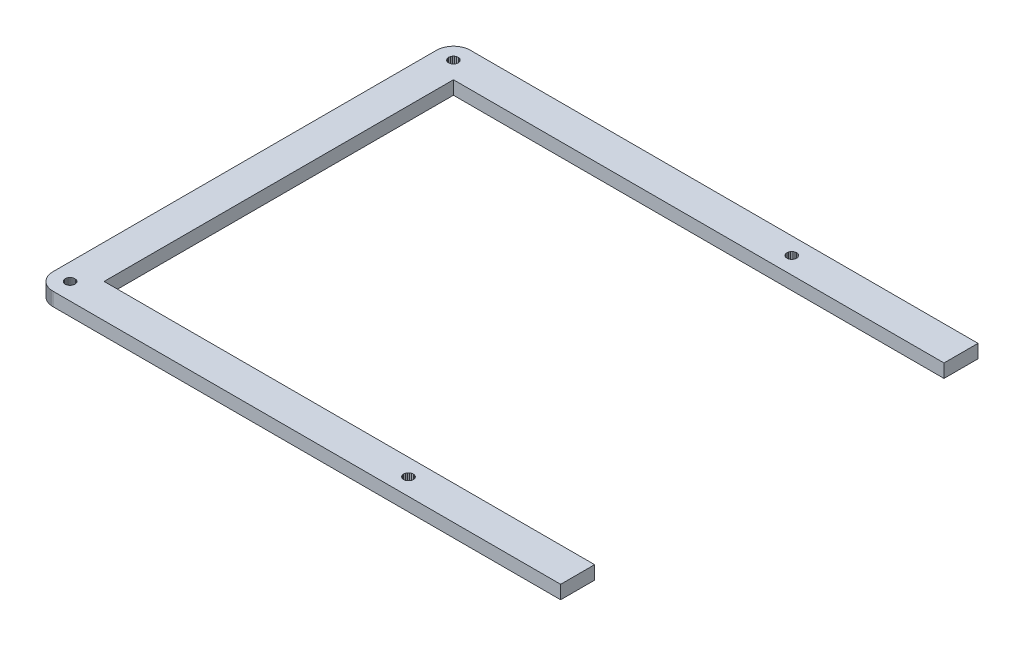
SolidWorks part; units mm, degrees
material "Copper"
ref_plane "Front Plane" through (0, 0, 0) normal (0, 0, 1) x (1, 0, 0)
ref_plane "Top Plane" through (0, 0, 0) normal (0, 1, 0) x (1, 0, 0)
ref_plane "Right Plane" through (0, 0, 0) normal (1, 0, 0) x (0, 0, -1)
sketch "Sketch1" plane through (0, 0, 0) normal (0, 1, 0) x (1, 0, 0)
  line L0 (365.806, 147.967) -> (366.279, 147.949)
  line L1 (366.279, 147.949) -> (366.748, 147.894)
  line L2 (366.748, 147.894) -> (367.21, 147.803)
  line L3 (367.21, 147.803) -> (367.661, 147.675)
  line L4 (367.661, 147.675) -> (368.106, 147.511)
  line L5 (368.106, 147.511) -> (368.533, 147.314)
  line L6 (368.533, 147.314) -> (368.942, 147.085)
  line L7 (368.942, 147.085) -> (369.334, 146.822)
  line L8 (369.334, 146.822) -> (369.704, 146.529)
  line L9 (369.704, 146.529) -> (370.05, 146.21)
  line L10 (370.05, 146.21) -> (370.371, 145.865)
  line L11 (370.371, 145.865) -> (370.664, 145.495)
  line L12 (370.664, 145.495) -> (370.925, 145.102)
  line L13 (370.925, 145.102) -> (371.154, 144.691)
  line L14 (371.154, 144.691) -> (371.352, 144.264)
  line L15 (371.352, 144.264) -> (371.514, 143.822)
  line L16 (371.514, 143.822) -> (371.641, 143.368)
  line L17 (371.641, 143.368) -> (371.733, 142.907)
  line L18 (371.733, 142.907) -> (371.789, 142.44)
  line L19 (371.789, 142.44) -> (371.807, 141.967)
  line L20 (371.807, 141.967) -> (371.807, 6.0909)
  line L21 (371.807, 6.0909) -> (371.789, 5.621)
  line L22 (371.789, 5.621) -> (371.733, 5.1539)
  line L23 (371.733, 5.1539) -> (371.641, 4.6909)
  line L24 (371.641, 4.6909) -> (371.514, 4.2375)
  line L25 (371.514, 4.2375) -> (371.352, 3.7951)
  line L26 (371.352, 3.7951) -> (371.154, 3.3679)
  line L27 (371.154, 3.3679) -> (370.925, 2.9573)
  line L28 (370.925, 2.9573) -> (370.664, 2.5645)
  line L29 (370.664, 2.5645) -> (370.371, 2.1966)
  line L30 (370.371, 2.1966) -> (370.05, 1.8493)
  line L31 (370.05, 1.8493) -> (369.704, 1.5296)
  line L32 (369.704, 1.5296) -> (369.334, 1.2375)
  line L33 (369.334, 1.2375) -> (368.942, 0.9757)
  line L34 (368.942, 0.9757) -> (368.533, 0.7455)
  line L35 (368.533, 0.7455) -> (368.106, 0.5498)
  line L36 (368.106, 0.5498) -> (367.661, 0.3859)
  line L37 (367.661, 0.3859) -> (367.21, 0.2577)
  line L38 (367.21, 0.2577) -> (366.748, 0.1654)
  line L39 (366.748, 0.1654) -> (366.279, 0.1102)
  line L40 (366.279, 0.1102) -> (365.806, 0.091)
  line L41 (365.806, 0.091) -> (6.095, 0.091)
  line L42 (6.095, 0.091) -> (5.6238, 0.1102)
  line L43 (5.6238, 0.1102) -> (5.1553, 0.1654)
  line L44 (5.1553, 0.1654) -> (4.6936, 0.2577)
  line L45 (4.6936, 0.2577) -> (4.2402, 0.3859)
  line L46 (4.2402, 0.3859) -> (3.7979, 0.5498)
  line L47 (3.7979, 0.5498) -> (3.3707, 0.7455)
  line L48 (3.3707, 0.7455) -> (2.96, 0.9757)
  line L49 (2.96, 0.9757) -> (2.5673, 1.2375)
  line L50 (2.5673, 1.2375) -> (2.198, 1.5296)
  line L51 (2.198, 1.5296) -> (1.8521, 1.8493)
  line L52 (1.8521, 1.8493) -> (1.5324, 2.1966)
  line L53 (1.5324, 2.1966) -> (1.2402, 2.5645)
  line L54 (1.2402, 2.5645) -> (0.9784, 2.9573)
  line L55 (0.9784, 2.9573) -> (0.7483, 3.3679)
  line L56 (0.7483, 3.3679) -> (0.5512, 3.7951)
  line L57 (0.5512, 3.7951) -> (0.3872, 4.2375)
  line L58 (0.3872, 4.2375) -> (0.2591, 4.6909)
  line L59 (0.2591, 4.6909) -> (0.1681, 5.1539)
  line L60 (0.1681, 5.1539) -> (0.113, 5.621)
  line L61 (0.113, 5.621) -> (0.0937, 6.0923)
  line L62 (0.0937, 6.0923) -> (0.0951, 141.967)
  line L63 (0.0951, 141.967) -> (0.113, 142.44)
  line L64 (0.113, 142.44) -> (0.1681, 142.907)
  line L65 (0.1681, 142.907) -> (0.2591, 143.368)
  line L66 (0.2591, 143.368) -> (0.3872, 143.822)
  line L67 (0.3872, 143.822) -> (0.5512, 144.264)
  line L68 (0.5512, 144.264) -> (0.7483, 144.691)
  line L69 (0.7483, 144.691) -> (0.9784, 145.102)
  line L70 (0.9784, 145.102) -> (1.2402, 145.495)
  line L71 (1.2402, 145.495) -> (1.5324, 145.865)
  line L72 (1.5324, 145.865) -> (1.8521, 146.21)
  line L73 (1.8521, 146.21) -> (2.198, 146.529)
  line L74 (2.198, 146.529) -> (2.5673, 146.822)
  line L75 (2.5673, 146.822) -> (2.96, 147.085)
  line L76 (2.96, 147.085) -> (3.3707, 147.314)
  line L77 (3.3707, 147.314) -> (3.7979, 147.511)
  line L78 (3.7979, 147.511) -> (4.2402, 147.675)
  line L79 (4.2402, 147.675) -> (4.6936, 147.803)
  line L80 (4.6936, 147.803) -> (5.1553, 147.894)
  line L81 (5.1553, 147.894) -> (5.6238, 147.949)
  line L82 (5.6238, 147.949) -> (6.095, 147.968)
  line L83 (6.095, 147.968) -> (365.806, 147.967)
  line L84 (365.252, 7.757) -> (364.769, 7.5117)
  line L85 (364.769, 7.5117) -> (364.388, 7.13)
  line L86 (364.388, 7.13) -> (364.141, 6.6504)
  line L87 (364.141, 6.6504) -> (364.06, 6.1157)
  line L88 (364.06, 6.1157) -> (364.141, 5.5838)
  line L89 (364.141, 5.5838) -> (364.388, 5.1029)
  line L90 (364.388, 5.1029) -> (364.769, 4.7211)
  line L91 (364.769, 4.7211) -> (365.252, 4.4759)
  line L92 (365.252, 4.4759) -> (365.781, 4.3918)
  line L93 (365.781, 4.3918) -> (366.317, 4.4759)
  line L94 (366.317, 4.4759) -> (366.797, 4.7211)
  line L95 (366.797, 4.7211) -> (367.178, 5.1029)
  line L96 (367.178, 5.1029) -> (367.425, 5.5838)
  line L97 (367.425, 5.5838) -> (367.506, 6.1157)
  line L98 (367.506, 6.1157) -> (367.425, 6.6504)
  line L99 (367.425, 6.6504) -> (367.178, 7.13)
  line L100 (367.178, 7.13) -> (366.797, 7.5117)
  line L101 (366.797, 7.5117) -> (366.317, 7.757)
  line L102 (366.317, 7.757) -> (365.781, 7.8411)
  line L103 (365.781, 7.8411) -> (365.252, 7.757)
  line L104 (245.361, 7.757) -> (244.88, 7.5117)
  line L105 (244.88, 7.5117) -> (244.5, 7.13)
  line L106 (244.5, 7.13) -> (244.255, 6.6504)
  line L107 (244.255, 6.6504) -> (244.169, 6.1157)
  line L108 (244.169, 6.1157) -> (244.255, 5.5838)
  line L109 (244.255, 5.5838) -> (244.5, 5.1029)
  line L110 (244.5, 5.1029) -> (244.88, 4.7211)
  line L111 (244.88, 4.7211) -> (245.361, 4.4759)
  line L112 (245.361, 4.4759) -> (245.894, 4.3918)
  line L113 (245.894, 4.3918) -> (246.428, 4.4759)
  line L114 (246.428, 4.4759) -> (246.908, 4.7211)
  line L115 (246.908, 4.7211) -> (247.29, 5.1029)
  line L116 (247.29, 5.1029) -> (247.536, 5.5838)
  line L117 (247.536, 5.5838) -> (247.62, 6.1157)
  line L118 (247.62, 6.1157) -> (247.536, 6.6504)
  line L119 (247.536, 6.6504) -> (247.29, 7.13)
  line L120 (247.29, 7.13) -> (246.908, 7.5117)
  line L121 (246.908, 7.5117) -> (246.428, 7.757)
  line L122 (246.428, 7.757) -> (245.894, 7.8411)
  line L123 (245.894, 7.8411) -> (245.361, 7.757)
  line L124 (125.473, 7.757) -> (124.992, 7.5117)
  line L125 (124.992, 7.5117) -> (124.612, 7.13)
  line L126 (124.612, 7.13) -> (124.365, 6.6504)
  line L127 (124.365, 6.6504) -> (124.281, 6.1157)
  line L128 (124.281, 6.1157) -> (124.365, 5.5838)
  line L129 (124.365, 5.5838) -> (124.612, 5.1029)
  line L130 (124.612, 5.1029) -> (124.992, 4.7211)
  line L131 (124.992, 4.7211) -> (125.473, 4.4759)
  line L132 (125.473, 4.4759) -> (126.007, 4.3918)
  line L133 (126.007, 4.3918) -> (126.54, 4.4759)
  line L134 (126.54, 4.4759) -> (127.021, 4.7211)
  line L135 (127.021, 4.7211) -> (127.403, 5.1029)
  line L136 (127.403, 5.1029) -> (127.648, 5.5838)
  line L137 (127.648, 5.5838) -> (127.732, 6.1157)
  line L138 (127.732, 6.1157) -> (127.648, 6.6504)
  line L139 (127.648, 6.6504) -> (127.403, 7.13)
  line L140 (127.403, 7.13) -> (127.021, 7.5117)
  line L141 (127.021, 7.5117) -> (126.54, 7.757)
  line L142 (126.54, 7.757) -> (126.007, 7.8411)
  line L143 (126.007, 7.8411) -> (125.473, 7.757)
  line L144 (5.5852, 7.757) -> (5.1056, 7.5117)
  line L145 (5.1056, 7.5117) -> (4.7239, 7.13)
  line L146 (4.7239, 7.13) -> (4.4786, 6.6504)
  line L147 (4.4786, 6.6504) -> (4.3932, 6.1157)
  line L148 (4.3932, 6.1157) -> (4.4786, 5.5838)
  line L149 (4.4786, 5.5838) -> (4.7239, 5.1029)
  line L150 (4.7239, 5.1029) -> (5.1056, 4.7211)
  line L151 (5.1056, 4.7211) -> (5.5852, 4.4759)
  line L152 (5.5852, 4.4759) -> (6.1185, 4.3918)
  line L153 (6.1185, 4.3918) -> (6.6532, 4.4759)
  line L154 (6.6532, 4.4759) -> (7.1327, 4.7211)
  line L155 (7.1327, 4.7211) -> (7.5145, 5.1029)
  line L156 (7.5145, 5.1029) -> (7.7597, 5.5838)
  line L157 (7.7597, 5.5838) -> (7.8438, 6.1157)
  line L158 (7.8438, 6.1157) -> (7.7597, 6.6504)
  line L159 (7.7597, 6.6504) -> (7.5145, 7.13)
  line L160 (7.5145, 7.13) -> (7.1327, 7.5117)
  line L161 (7.1327, 7.5117) -> (6.6532, 7.757)
  line L162 (6.6532, 7.757) -> (6.1185, 7.8411)
  line L163 (6.1185, 7.8411) -> (5.5852, 7.757)
  line L164 (12.1447, 135.919) -> (359.759, 135.919)
  line L165 (359.759, 135.919) -> (359.759, 12.1405)
  line L166 (359.759, 12.1405) -> (12.1447, 12.1405)
  line L167 (12.1447, 12.1405) -> (12.1447, 135.919)
  line L168 (125.473, 143.583) -> (124.992, 143.338)
  line L169 (124.992, 143.338) -> (124.612, 142.956)
  line L170 (124.612, 142.956) -> (124.365, 142.477)
  line L171 (124.365, 142.477) -> (124.281, 141.942)
  line L172 (124.281, 141.942) -> (124.365, 141.409)
  line L173 (124.365, 141.409) -> (124.612, 140.929)
  line L174 (124.612, 140.929) -> (124.992, 140.547)
  line L175 (124.992, 140.547) -> (125.473, 140.302)
  line L176 (125.473, 140.302) -> (126.007, 140.217)
  line L177 (126.007, 140.217) -> (126.54, 140.302)
  line L178 (126.54, 140.302) -> (127.021, 140.547)
  line L179 (127.021, 140.547) -> (127.403, 140.929)
  line L180 (127.403, 140.929) -> (127.648, 141.409)
  line L181 (127.648, 141.409) -> (127.732, 141.942)
  line L182 (127.732, 141.942) -> (127.648, 142.477)
  line L183 (127.648, 142.477) -> (127.403, 142.956)
  line L184 (127.403, 142.956) -> (127.021, 143.338)
  line L185 (127.021, 143.338) -> (126.54, 143.583)
  line L186 (126.54, 143.583) -> (126.007, 143.667)
  line L187 (126.007, 143.667) -> (125.473, 143.583)
  line L188 (245.361, 143.583) -> (244.88, 143.338)
  line L189 (244.88, 143.338) -> (244.5, 142.956)
  line L190 (244.5, 142.956) -> (244.255, 142.477)
  line L191 (244.255, 142.477) -> (244.169, 141.942)
  line L192 (244.169, 141.942) -> (244.255, 141.409)
  line L193 (244.255, 141.409) -> (244.5, 140.929)
  line L194 (244.5, 140.929) -> (244.88, 140.547)
  line L195 (244.88, 140.547) -> (245.361, 140.302)
  line L196 (245.361, 140.302) -> (245.894, 140.217)
  line L197 (245.894, 140.217) -> (246.428, 140.302)
  line L198 (246.428, 140.302) -> (246.908, 140.547)
  line L199 (246.908, 140.547) -> (247.29, 140.929)
  line L200 (247.29, 140.929) -> (247.536, 141.409)
  line L201 (247.536, 141.409) -> (247.62, 141.942)
  line L202 (247.62, 141.942) -> (247.536, 142.477)
  line L203 (247.536, 142.477) -> (247.29, 142.956)
  line L204 (247.29, 142.956) -> (246.908, 143.338)
  line L205 (246.908, 143.338) -> (246.428, 143.583)
  line L206 (246.428, 143.583) -> (245.894, 143.667)
  line L207 (245.894, 143.667) -> (245.361, 143.583)
  line L208 (365.252, 143.583) -> (364.769, 143.338)
  line L209 (364.769, 143.338) -> (364.388, 142.956)
  line L210 (364.388, 142.956) -> (364.141, 142.477)
  line L211 (364.141, 142.477) -> (364.06, 141.942)
  line L212 (364.06, 141.942) -> (364.141, 141.409)
  line L213 (364.141, 141.409) -> (364.388, 140.929)
  line L214 (364.388, 140.929) -> (364.769, 140.547)
  line L215 (364.769, 140.547) -> (365.252, 140.302)
  line L216 (365.252, 140.302) -> (365.781, 140.217)
  line L217 (365.781, 140.217) -> (366.317, 140.302)
  line L218 (366.317, 140.302) -> (366.797, 140.547)
  line L219 (366.797, 140.547) -> (367.178, 140.929)
  line L220 (367.178, 140.929) -> (367.425, 141.409)
  line L221 (367.425, 141.409) -> (367.506, 141.942)
  line L222 (367.506, 141.942) -> (367.425, 142.477)
  line L223 (367.425, 142.477) -> (367.178, 142.956)
  line L224 (367.178, 142.956) -> (366.797, 143.338)
  line L225 (366.797, 143.338) -> (366.317, 143.583)
  line L226 (366.317, 143.583) -> (365.781, 143.667)
  line L227 (365.781, 143.667) -> (365.252, 143.583)
  line L228 (5.5852, 143.583) -> (5.1056, 143.338)
  line L229 (5.1056, 143.338) -> (4.7239, 142.956)
  line L230 (4.7239, 142.956) -> (4.4786, 142.477)
  line L231 (4.4786, 142.477) -> (4.3932, 141.942)
  line L232 (4.3932, 141.942) -> (4.4786, 141.409)
  line L233 (4.4786, 141.409) -> (4.7239, 140.929)
  line L234 (4.7239, 140.929) -> (5.1056, 140.547)
  line L235 (5.1056, 140.547) -> (5.5852, 140.302)
  line L236 (5.5852, 140.302) -> (6.1185, 140.217)
  line L237 (6.1185, 140.217) -> (6.6532, 140.302)
  line L238 (6.6532, 140.302) -> (7.1327, 140.547)
  line L239 (7.1327, 140.547) -> (7.5145, 140.929)
  line L240 (7.5145, 140.929) -> (7.7597, 141.409)
  line L241 (7.7597, 141.409) -> (7.8438, 141.942)
  line L242 (7.8438, 141.942) -> (7.7597, 142.477)
  line L243 (7.7597, 142.477) -> (7.5145, 142.956)
  line L244 (7.5145, 142.956) -> (7.1327, 143.338)
  line L245 (7.1327, 143.338) -> (6.6532, 143.583)
  line L246 (6.6532, 143.583) -> (6.1185, 143.667)
  line L247 (6.1185, 143.667) -> (5.5852, 143.583)
  line L248 (185.9505, 147.9675) -> (185.9505, 0.091)
extrude "Boss-Extrude2" add sketch "Sketch1" along normal blind 4.7625 contours L248 L83 L82 L81 L80 L79 L78 L77 L76 L75 L74 L73 L72 L71 L70 L69 L68 L67 L66 L65 L64 L63 L62 L61 L60 L59 L58 L57 L56 L55 L54 L53 L52 L51 L50 L49 L48 L47 L46 L45 L44 L43 L42 L41 L166 L167 L164 L247 L246 region at (183.5754, 0, -141.9433)
